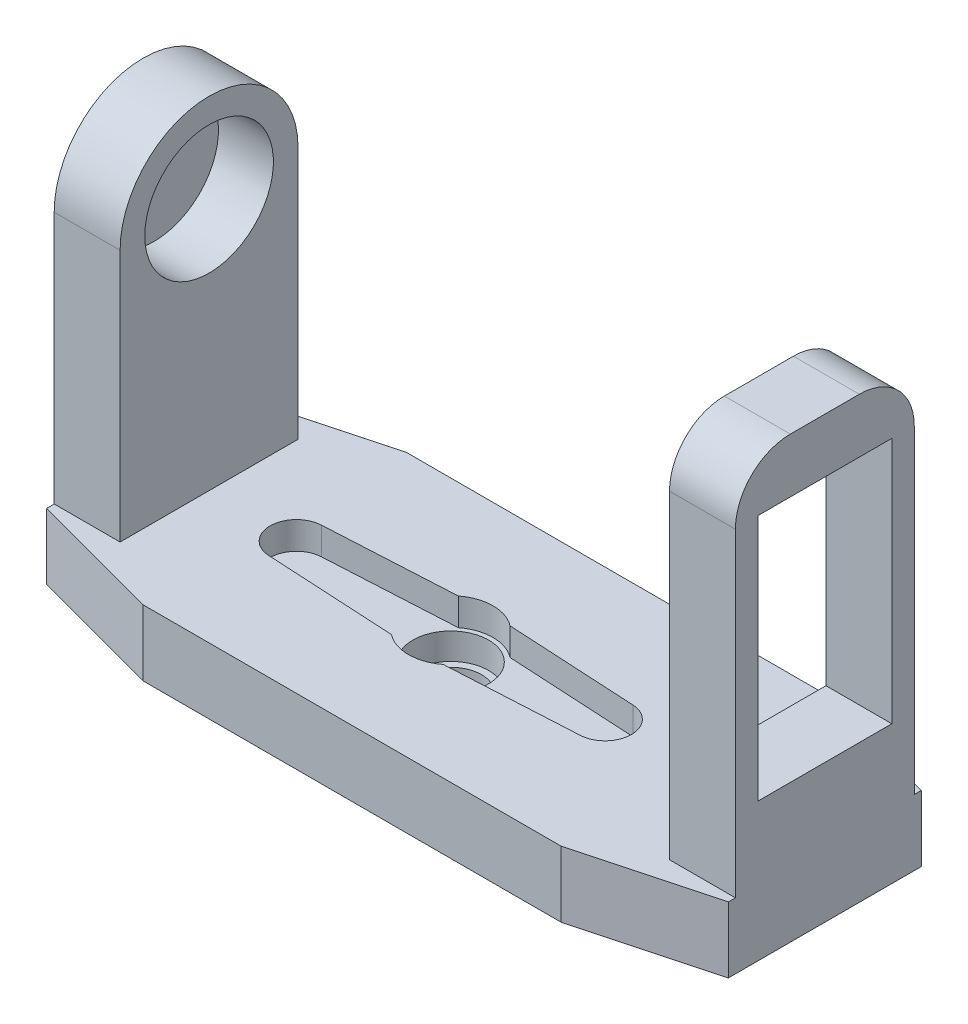
SolidWorks part; units mm, degrees
ref_plane "前视基准面" through (0, 0, 0) normal (0, 0, 1) x (1, 0, 0)
ref_plane "上视基准面" through (0, 0, 0) normal (0, 1, 0) x (1, 0, 0)
ref_plane "右视基准面" through (0, 0, 0) normal (1, 0, 0) x (0, 0, -1)
sketch "草图1" plane through (0, 0, 0) normal (0, 1, 0) x (1, 0, 0)
  line L0 (0, 0) -> (3.025, 0) construction
  line L1 (34.05, -12) -> (-28, -12)
  line L2 (34.05, -12) -> (34.05, 12)
  line L3 (34.05, 12) -> (-28, 12)
  line L4 (-28, -12) -> (-28, 12)
  line L5 (34.05, -12) -> (-28, 12) construction
  line L6 (34.05, 12) -> (-28, -12) construction
  point P0 (0, 0)
  dimension "D1" = 28
  dimension "D2" = 34.05
  dimension "D3" = 24
extrude "凸台-拉伸1" add sketch "草图1" along normal blind 6
chamfer "倒角1" distance 12 angle 15 4 edges at (34.05, 3, -12) (34.05, 3, 12) (-28, 3, 12) (-28, 3, -12) first distance on face at (3.025, 3, -12) first distance on face at (3.025, 3, 12)
sketch "草图2" plane through (-28, 0, 0) normal (-1, 0, 0) x (0, 0, 1)
  line L0 (-8.7846, 6) -> (8.7846, 6) construction
  line L1 (8.0991, 37.0991) -> (-8.0991, 37.0991)
  line L2 (8.0991, 37.0991) -> (8.0991, 6)
  line L3 (8.0991, 6) -> (-8.0991, 6)
  line L4 (-8.0991, 37.0991) -> (-8.0991, 6)
  line L5 (8.0991, 37.0991) -> (-8.0991, 6) construction
  line L6 (8.0991, 6) -> (-8.0991, 37.0991) construction
  line L7 (0, 21.5496) -> (0, 6) construction
  circle A0 centre (0, 29) radius 5.8528
  circle A1 centre (0, 29) radius 8.0991 construction
  point P0 (0, 21.5496)
  dimension "D1" = 23
extrude "凸台-拉伸2" add sketch "草图2" against normal blind 6
sketch "草图8" plane through (-28, 0, 0) normal (-1, 0, 0) x (0, 0, 1)
  circle A0 centre (0, 29) radius 5.8528
extrude "凸台-拉伸4" add sketch "草图8" against normal blind 1
fillet "圆角1" 2 edges at (-25, 37.0991, -8.0991) (-25, 37.0991, 8.0991) type full round first side face at (-25, 21.5496, -8.0991) second side face at (-25, 21.5496, 8.0991) middle face at (-25, 37.0991, 0)
sketch "草图3" plane through (34.05, 0, 0) normal (1, 0, 0) x (0, 0, -1)
  line L1 (8.141, 40.0563) -> (-8.141, 40.0563)
  line L2 (8.141, 40.0563) -> (8.141, 6)
  line L3 (8.141, 6) -> (-8.141, 6)
  line L4 (-8.141, 40.0563) -> (-8.141, 6)
  line L5 (8.141, 40.0563) -> (-8.141, 6) construction
  line L6 (8.141, 6) -> (-8.141, 40.0563) construction
  line L7 (0, 23.85) -> (0, 0) construction
  line L8 (6.1, 35.1) -> (-6.1, 35.1)
  line L9 (6.1, 35.1) -> (6.1, 12.6)
  line L10 (6.1, 12.6) -> (-6.1, 12.6)
  line L11 (-6.1, 35.1) -> (-6.1, 12.6)
  line L12 (6.1, 35.1) -> (-6.1, 12.6) construction
  line L13 (6.1, 12.6) -> (-6.1, 35.1) construction
  line L17 (-8.7846, 6) -> (8.7846, 6) construction
  circle A0 centre (0, 29) radius 5.8528 construction
  circle A1 centre (0, 29) radius 5.8528 construction
  point P0 (0, 23.0282)
  point P7 (0, 23.85)
  dimension "D1" = 22.5
  dimension "D2" = 12.2
  dimension "D3" = 6.1
extrude "凸台-拉伸3" add sketch "草图3" against normal blind 6
fillet "圆角2" radius 5 2 edges at (31.05, 40.0563, 8.141) (31.05, 40.0563, -8.141)
sketch "草图4" plane through (-24, 6, 6) normal (0, -1, 0) x (-1, 0, 0)
  line L0 (-24, 6) -> (-9.95, 6) construction
  line L1 (-9.8409, 4.003) -> (-21.7909, 3.35) construction
  line L2 (-21.7909, 8.65) -> (-9.8409, 7.997) construction
  line L3 (-21.6407, 9.0424) -> (-9.8191, 8.3964)
  line L4 (-9.8191, 3.6036) -> (-21.6407, 2.9576)
  arc A0 (-21.7909, 8.65) -> (-21.7909, 3.35) centre (-24, 6) ccw construction
  arc A1 (-9.8409, 4.003) -> (-9.8409, 7.997) centre (-9.95, 6) ccw construction
  arc A2 (-9.8191, 3.6036) -> (-9.8191, 8.3964) centre (-9.95, 6) ccw
  arc A3 (-21.6407, 9.0424) -> (-21.6407, 2.9576) centre (-24, 6) ccw
  dimension "D1" = 6.9
  dimension "D2" = 4
  dimension "D3" = 19.5
  dimension "D4" = 5.3
  dimension "D5" = 0.4
extrude "切除-拉伸1" cut sketch "草图4" along normal blind 2.5
mirror "镜向1" about plane through (0, 0, 0) normal (1, 0, 0) of "切除-拉伸1"
sketch "草图5" plane through (0, 3.5, 0) normal (0, 1, 0) x (1, 0, 0)
  circle A0 centre (0, 0) radius 3.45
extrude "切除-拉伸2" cut sketch "草图5" against normal blind 2.4
sketch "草图6" plane through (0, 1.1, 0) normal (0, 1, 0) x (1, 0, 0)
  circle A0 centre (0, 0) radius 2.8
  dimension "D1" = 5.6
extrude "切除-拉伸3" cut sketch "草图6" against normal through all
